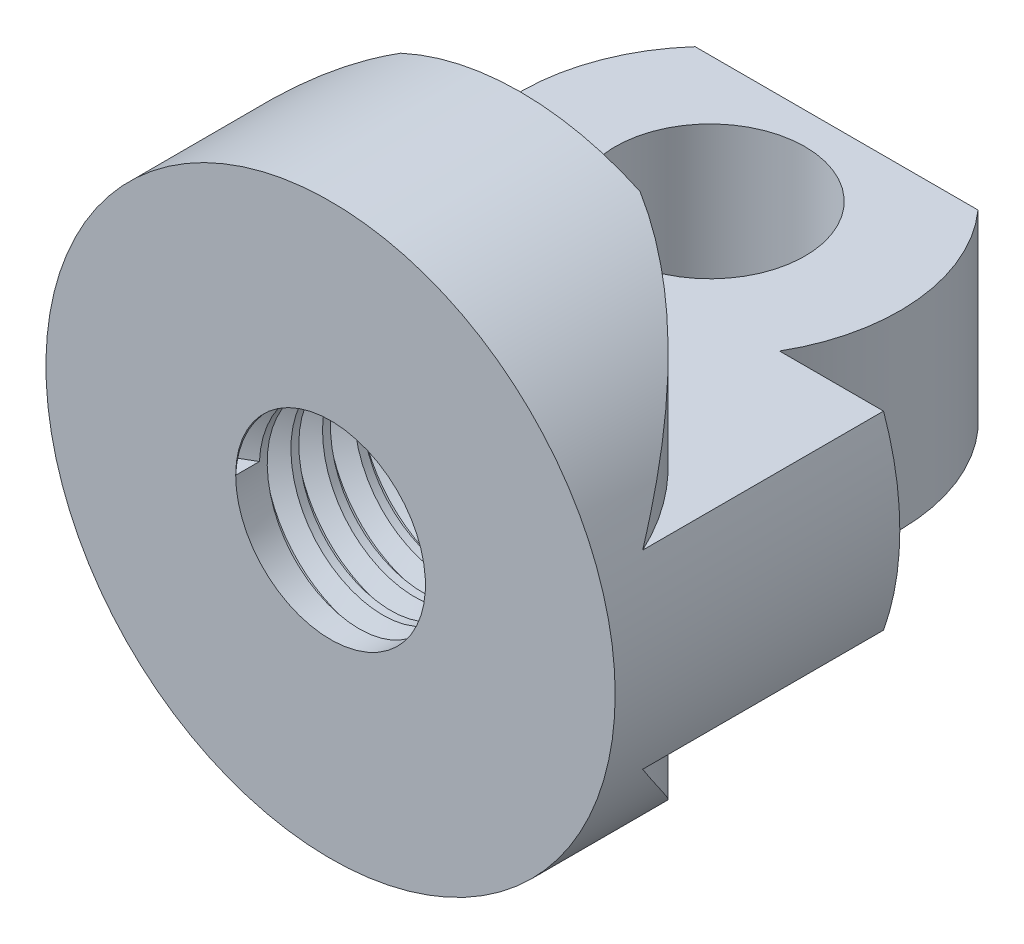
SolidWorks part; units mm, degrees
ref_plane "Alzado" through (0, 0, 0) normal (0, 0, 1) x (1, 0, 0)
ref_plane "Planta" through (0, 0, 0) normal (0, 1, 0) x (1, 0, 0)
ref_plane "Vista lateral" through (0, 0, 0) normal (1, 0, 0) x (0, 0, -1)
sketch "Croquis1" plane through (0, 0, 0) normal (0, 0, 1) x (1, 0, 0)
  circle A0 centre (0, 0) radius 1.5
  circle A1 centre (0, 0) radius 4.5
  dimension "D1" = 3
  dimension "D2" = 3
extrude "Saliente-Extruir2" add sketch "Croquis1" along normal blind 3
thread "Rosca1" pitch 0.5 method cut profile "Perfil de rosca1" start angle 0, offset 0, length 0, pitch 0.5, diameter 3
ref_plane "Plano1" through (-1.5, 0, 3) normal (0, -1, 0) x (-1, 0, 0)
sketch "Perfil de rosca1" plane through (-1.5, 0, 3) normal (0, -1, 0) x (-1, 0, 0)
  line L0 (0, 0) -> (0, 0.5) construction
  line L1 (0, 0) -> (0.2706, 0.1562)
  line L2 (0.2706, 0.1562) -> (0.2706, 0.2187)
  line L3 (0.2706, 0.2187) -> (0, 0.375)
  line L4 (0.2706, 0.1875) -> (0, 0.1875) construction
  line L11 (0, 0) -> (0, 0.375)
  point P2 (0, 0)
  dimension "Pitch" = 0.5
  dimension "Profile_Angle" = 60
  dimension "Profile_Land" = 0.0625
  dimension "Profile_Height" = 0.2706
sketch "Croquis5" plane through (0, 0, 0) normal (0, 1, 0) x (1, 0, 0)
  line L1 (-4.5, 0) -> (4.5, 0)
  line L2 (-4.5, 0) -> (-4.5, 5)
  line L3 (-4.5, 5) -> (4.5, 5)
  line L4 (4.5, 0) -> (4.5, 5)
  circle A0 centre (0, 3) radius 1.5
  dimension "D2" = 3
  dimension "D1" = 5
  dimension "D3" = 3
extrude "Saliente-Extruir3" add sketch "Croquis5" along normal mid plane 8
sketch "Croquis6" plane through (0, 0, 0) normal (0, 0, 1) x (1, 0, 0)
  line L0 (2.0616, 4) -> (4.5, 4) construction
  line L1 (4.5, 4) -> (4.5, 0) construction
  line L2 (4.5, 0) -> (4.5, -4) construction
  line L3 (2.0616, -4) -> (4.5, -4) construction
  line L4 (-4.5, -4) -> (-2.0616, -4) construction
  line L5 (-4.5, 0) -> (-4.5, -4) construction
  line L6 (-4.5, 4) -> (-2.0616, 4) construction
  line L7 (-4.5, 4) -> (-4.5, 0) construction
  line L8 (2.0616, 4) -> (4.5, 4)
  line L9 (4.5, 4) -> (4.5, 0)
  line L10 (4.5, 0) -> (4.5, -4)
  line L11 (2.0616, -4) -> (4.5, -4)
  line L12 (-4.5, -4) -> (-2.0616, -4)
  line L13 (-4.5, 0) -> (-4.5, -4)
  line L14 (-4.5, 4) -> (-2.0616, 4)
  line L15 (-4.5, 4) -> (-4.5, 0)
  circle A0 centre (0, 0) radius 4.5 construction
  arc A1 (-2.0616, 4) -> (-2.0616, -4) centre (0, 0) ccw
  arc A2 (2.0616, -4) -> (2.0616, 4) centre (0, 0) ccw
extrude "Cortar-Extruir3" cut sketch "Croquis6" against normal blind 10 contours A1 L14 L15 | A2 L9 L8 | A2 L11 L10 | A1 L13 L12 region at (3.822, -3.0619, 0) region at (3.822, 3.0619, 0) region at (-3.822, -3.0619, 0) region at (-3.822, 3.0619, 0)
sketch "Croquis7" plane through (0, 0, 0) normal (1, 0, 0) x (0, 0, -1)
  line L0 (5, -4) -> (5, 4) construction
  line L1 (0, 1.5) -> (5, 1.5)
  line L3 (0, -1.5) -> (5, -1.5)
  line L4 (5, 1.5) -> (5, -1.5)
  line L5 (2.5, -1.5) -> (2.5, -4.5) construction
  line L6 (0, 4.5) -> (5, 4.5)
  line L7 (0, 4.5) -> (0, -4.5)
  line L8 (0, -4.5) -> (5, -4.5)
  line L9 (5, 4.5) -> (5, -4.5)
  line L10 (-3, -4.5) -> (0, -4.5) construction
  line L11 (-3, -4.5) -> (0, -4.5)
  line L12 (2.5, 4.5) -> (2.5, 1.5) construction
  dimension "D2" = 3
extrude "Cortar-Extruir4" cut sketch "Croquis7" against normal mid plane 20 contours L9 L6 L7 L1 | L9 L3 L7 L8 region at (0, 3, -2.5) region at (0, -3, -2.5)
sketch "Croquis9" plane through (0, 1.5, 0) normal (0, 1, 0) x (1, 0, 0)
  line L1 (4.5, -3) -> (4.5, 5) construction
  line L2 (-4.5, -3) -> (4.5, -3) construction
  line L3 (-4.5, -3) -> (4.5, -3)
  line L4 (-4.5, -3) -> (4.5, -3)
  line L5 (-4.5, -3) -> (-4.5, 0.4)
  line L6 (-4.5, 0.4) -> (4.5, 0.4)
  line L7 (4.5, -3) -> (4.5, 0.4)
  arc A0 (-4.5, -3) -> (4.5, -3) centre (0, -4.2779) cw
  point P7 (0, 0.4)
  line M3 (-4.2426, 0) -> (0, 0)
  line M5 (0.2861, 0) -> (4.2426, 0)
  line M6 (4.2426, 0) -> (4.2426, 5)
  line M8 (-4.2426, 5) -> (-4.2426, 0)
  dimension "D1" = 3.4
extrude "Cortar-Extruir6" cut sketch "Croquis9" along normal blind 10 contours A0 L6 M3 M8 | L5 A0 L6 M3 M8 | L6 A0 M5 M6 | A0 L7 L6 M5 M6 region at (-3.7837, 1.5, 0.7956) region at (3.7837, 1.5, 0.7956) region at (-2.7246, 1.5, -0.2169) region at (2.7246, 1.5, -0.2169)
mirror "Simetría1" about plane through (0, 0, 0) normal (0, 1, 0) of "Cortar-Extruir6"
sketch "Croquis10" plane through (0, 1.5, 0) normal (0, 1, 0) x (1, 0, 0)
  line L0 (-4.5, 5) -> (-4.5, -3) construction
  line L1 (-4.5, 1.5) -> (4.5, 1.5)
  line L2 (-4.5, 1.5) -> (-4.5, 5)
  line L3 (-4.5, 5) -> (4.5, 5)
  line L4 (4.5, 1.5) -> (4.5, 5)
  line L5 (1.8927, 0) -> (-1.8927, 0) construction
  line L6 (1.8927, 0) -> (1.8835, 0)
  line L7 (-1.8835, 0) -> (-1.8927, 0)
  circle A0 centre (0, 3) radius 1.5 construction
  circle A1 centre (0, 3) radius 1.5
  arc A2 (-2.2361, 5) -> (-2.5981, 1.5) centre (0, 3) ccw
  arc A3 (2.5981, 1.5) -> (2.2361, 5) centre (0, 3) ccw
  line M8 (4.2426, -2.3074) -> (4.2426, 5)
  line M9 (4.2426, 5) -> (-4.2426, 5)
  line M10 (-4.2426, 5) -> (-4.2426, -2.3074)
  dimension "D1" = 3
extrude "Cortar-Extruir7" cut sketch "Croquis10" against normal blind 10 contours A2 L3 L1 M10 | A3 L1 M8 M9 | L3 L2 L1 M10 | L1 L4 L3 M8 region at (-4.3713, 1.5, -3.25) region at (-3.5119, 1.5, -3.3171) region at (3.5119, 1.5, -3.3171) region at (4.3713, 1.5, -3.25)
